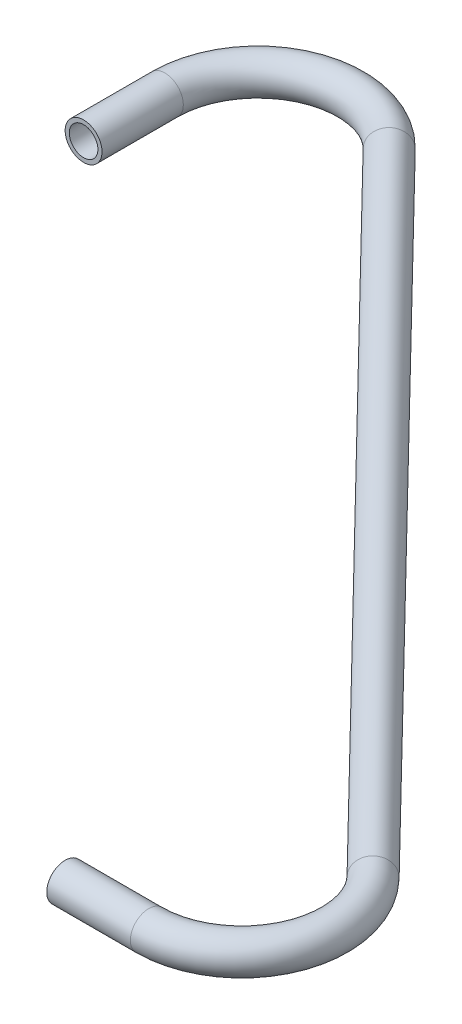
SolidWorks part; units mm, degrees
ref_plane "Front Plane" through (0, 0, 0) normal (0, 0, 1) x (1, 0, 0)
ref_plane "Top Plane" through (0, 0, 0) normal (0, 1, 0) x (1, 0, 0)
ref_plane "Right Plane" through (0, 0, 0) normal (1, 0, 0) x (0, 0, -1)
sketch3d "3DSketch1"
  line L0 (0, 0, 0) -> (14.4032, 0, 0)
  line L1 (25.8603, 0, -27.1684) -> (-81.3746, 0, -137.1752)
  line L3 (-108.8318, 0, -126.0068) -> (-108.8318, 0, -112.0068)
  arc A0 (-108.8318, 0, -126.0068) -> (-81.3746, 0, -137.1752) centre (-92.8318, 0, -126.0068) ccw
  arc A2 (14.4032, 0, 0) -> (25.8603, 0, -27.1684) centre (14.4032, 0, -16) ccw
  point P9 (-92.8318, -16, -126.0068)
  point P17 (14.4032, 16, -16)
  dimension "D5" = 16
  dimension "D7" = 16
  dimension "D1" = 108.8318
  dimension "D6" = 153.6256
  dimension "D2" = 156.1726
  dimension "D3" = 14
  dimension "D4" = 14.4032
sketch "Sketch2" plane through (0, 0, 0) normal (1, 0, 0) x (0, 0, -1)
  circle A0 centre (0, 0) radius 3.175
  dimension "D1" = 6.35
sweep "Sweep-Thin1" add profiles "Sketch2" path "3DSketch1" parameters "D1"=0.7112
